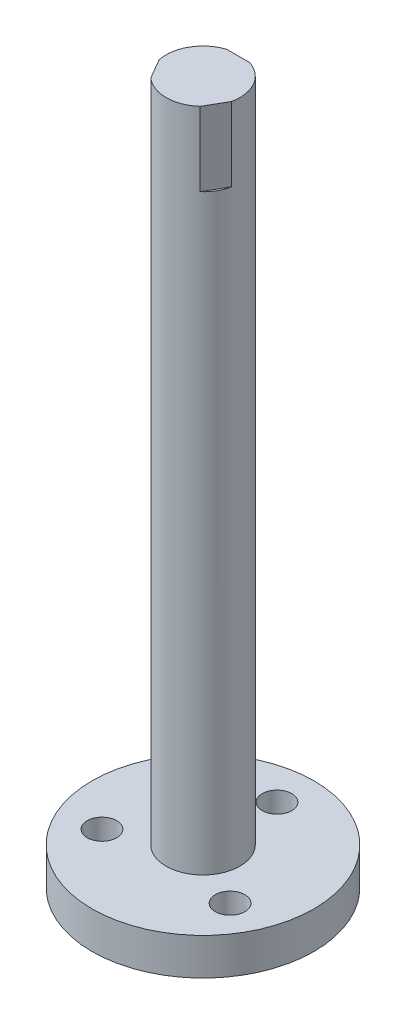
SolidWorks part; units mm, degrees
material "Plain Carbon Steel"
ref_plane "Front Plane" through (0, 0, 0) normal (0, 0, 1) x (1, 0, 0)
ref_plane "Top Plane" through (0, 0, 0) normal (0, 1, 0) x (1, 0, 0)
ref_plane "Right Plane" through (0, 0, 0) normal (1, 0, 0) x (0, 0, -1)
sketch "Sketch1" plane through (0, 0, 0) normal (0, 1, 0) x (1, 0, 0)
  circle A0 centre (0, 0) radius 15
  dimension "D1" = 30
extrude "Boss-Extrude1" add sketch "Sketch1" against normal blind 5
sketch "Sketch2" plane through (0, 0, 0) normal (0, 1, 0) x (1, 0, 0)
  circle A0 centre (0, 0) radius 5
  dimension "D1" = 10
extrude "Boss-Extrude2" add sketch "Sketch2" along normal blind 90
sketch "Sketch3" plane through (0, 0, 0) normal (0, 1, 0) x (1, 0, 0)
  circle A0 centre (-8.6603, -5) radius 2.05 construction
  circle A1 centre (8.6603, -5) radius 2.05 construction
  circle A2 centre (0, 10) radius 2.05 construction
  circle A3 centre (-8.6603, -5) radius 2.05
  circle A4 centre (8.6603, -5) radius 2.05
  circle A5 centre (0, 10) radius 2.05
hole_wizard "Ø4.0mm Dowel Hole1" positions "Sketch6" profile "Sketch5" hole size "Ø4.0" standard "ISO" end condition through all
sketch "Sketch6" plane through (0, 0, 0) normal (0, 1, 0) x (1, 0, 0)
  point P0 (8.6603, -5)
  point P3 (-8.6603, -5)
  point P6 (0, 10)
sketch "Sketch5" plane through (8.6603, 0, 5) normal (1, 0, 0) x (0, 0, 1)
  line L0 (0, 0) -> (0, 5)
  line L1 (0, 5) -> (2, 5)
  line L2 (2, 5) -> (2, 0)
  line L5 (2, 0) -> (0, 0)
  line L11 (0, -6.35) -> (0, 107.95) construction
  dimension "Thru Hole Dia." = 4
  dimension "Thru Hole Depth" = 5
sketch "Sketch7" plane through (0, 90, 0) normal (0, 1, 0) x (1, 0, 0)
  line L0 (-1.5612, 4.75) -> (1.5612, 4.75)
  circle A0 centre (0, 0) radius 5 construction
  arc A1 (1.5612, 4.75) -> (-1.5612, 4.75) centre (0, 0) ccw
  dimension "D1" = 0.25
extrude "Cut-Extrude2" cut sketch "Sketch7" against normal blind 10 contours L0 A1
pattern_circular "CirPattern1" count 3 every 120 about axis through (0, 90, 0) along (0, 1, 0) of "Cut-Extrude2"
